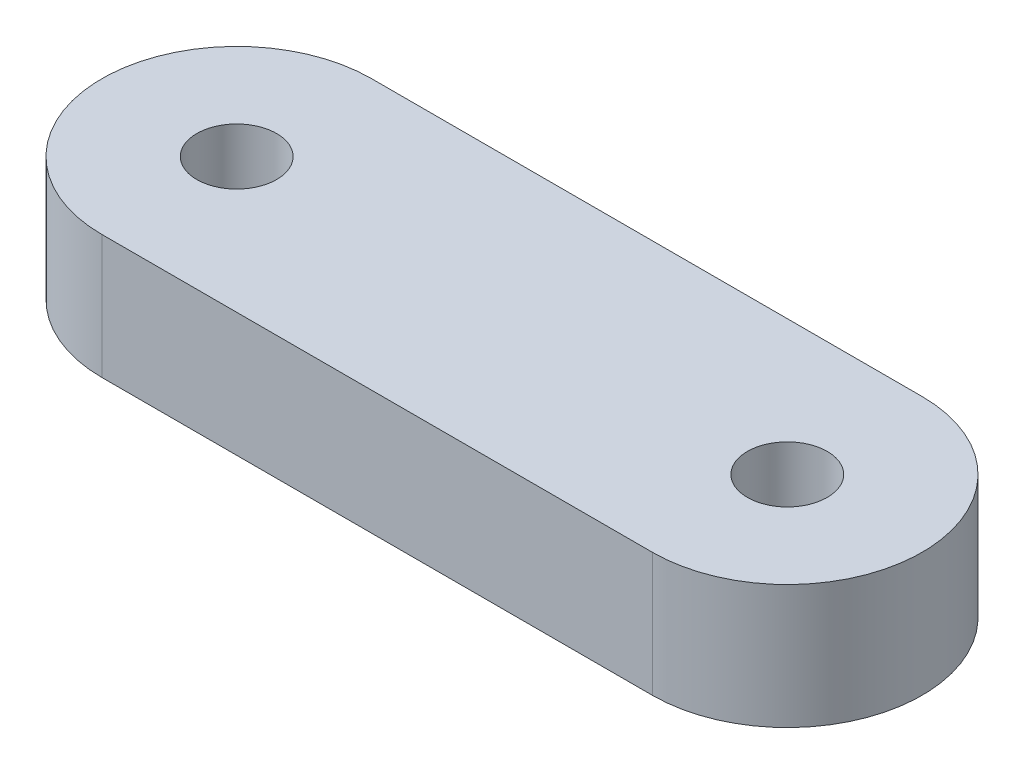
SolidWorks part; units mm, degrees
ref_plane "Front Plane" through (0, 0, 0) normal (0, 0, 1) x (1, 0, 0)
ref_plane "Top Plane" through (0, 0, 0) normal (0, 1, 0) x (1, 0, 0)
ref_plane "Right Plane" through (0, 0, 0) normal (1, 0, 0) x (0, 0, -1)
sketch "Sketch1" plane through (0, 0, 0) normal (0, 1, 0) x (1, 0, 0)
  line L0 (14.9, 0) -> (14.9, 15.5804) construction
  line L1 (-10, 4.9) -> (10, 4.9)
  line L2 (-14.9, 0) -> (-14.9, 15.5804) construction
  line L3 (-10, -4.9) -> (10, -4.9)
  line L4 (-10, 4.9) -> (-10, -4.9) construction
  line L5 (-10, 4.9) -> (10, -4.9) construction
  line L6 (-10, -4.9) -> (10, 4.9) construction
  line L7 (10, 4.9) -> (10, -4.9) construction
  line L8 (0, 4.9) -> (0, -4.9) construction
  arc A0 (-10, 4.9) -> (-10, -4.9) centre (-10, 0) ccw
  arc A1 (10, -4.9) -> (10, 4.9) centre (10, 0) ccw
  circle A2 centre (-10, 0) radius 1.45
  circle A3 centre (10, 0) radius 1.45
  point P0 (0, 0)
  dimension "D4" = 4.9
  dimension "D5" = 2.9
  dimension "D1" = 9.8
  dimension "D2" = 20
extrude "Boss-Extrude1" add sketch "Sketch1" along normal blind 4.5
equation "\"Y-ROD-SPACING\"=75"
equation "\"Y-BED-OFFSET\"=2"
equation "\"Y-BED-ROD-INSET\"=3.5"
equation "\"T-SLOT-NUT-FILLET-RADIUS\"=0.5"
equation "\"T-SLOT-SCREW-SHAFT-RADIUS\"=1.55"
equation "\"T-SLOT-SCREW-SHAFT-CUTOUT-LENGTH\"=11.0"
equation "\"T-SLOT-NUT-DEPTH\"=3.5"
equation "\"T-SLOT-NUT-WIDTH\"=2.85"
equation "\"T-SLOT-NUT-END-DISTANCE\"=8"
equation "\"ACRYLIC-TAB-CUTOUT-SIZE\"=\"ACRYLIC-THICKNESS\"+\"ACRYLIC-TAB-TOLERANCE\"*2"
equation "\"ACRYLIC-M3-HOLE\"=2.9"
equation "\"D5@Sketch1\"=\"ACRYLIC-M3-HOLE\""
equation "\"SMOOTHROD-CAP-SCREW-DISTANCE\"=20"
equation "\"D2@Sketch1\"=\"SMOOTHROD-CAP-SCREW-DISTANCE\""
equation "\"X-ROD-SPACING\"=45"
equation "\"Z-ROD-SPACING\"=17.5"
equation "\"ACRYLIC-THICKNESS\"=10"
equation "\"ACRYLIC-THICKNESS2\"=4.5"
equation "\"ACRYLIC-TAB-WIDTH\"=\"ACRYLIC-THICKNESS\""
equation "\"FRAME-WIDTH-INNER\"=370"
equation "\"NEMA17-HOLE-SPACING\"=31"
equation "\"NEMA17-CENTRAL-CUTOUT\"=22.5"
equation "\"Z-BRACKET-REACH\"=55"
equation "\"TOP-BRACKET-SPACING\"=40"
equation "\"SMOOTHROD-X-LENGTH\"=350"
equation "\"SMOOTHROD-Y-LENGTH\"=350"
equation "\"SMOOTHROD-Z-LENGTH\"=350"
equation "\"SMOOTHROD-TIGHTENING-HEADROOM\"=.25"
equation "\"LEADSCREW-Z-LENGTH\"=300"
equation "\"SCREW-LENGTH-FRAME\"=\"ACRYLIC-THICKNESS\" + 10"
equation "\"SCREW-HEAD-RADIUS\"=6"
equation "\"PRINTED-X-SMOOTHROD-DIAMETER\"=9.0"
equation "\"PRINTED-X-SMOOTHROD-CUTOUT\"=10"
equation "\"PRINTED-X-BASE-HEIGHT\"=10"
equation "\"PRINTED-LM8UU-CUTOUT-SIZE\"=15.5"
equation "\"PRINTED-LM8UU-CUTOUT-LENGTH\"=24.5"
equation "\"PRINTED-X-IDLER-HEIGHT\"=16"
equation "\"PSU-MOUNTING-WIDTH\"=95"
equation "\"PSU-MOUNTING-HEIGHT\"=177"
equation "\"D1@Boss-Extrude1\"=\"ACRYLIC-THICKNESS2\""
